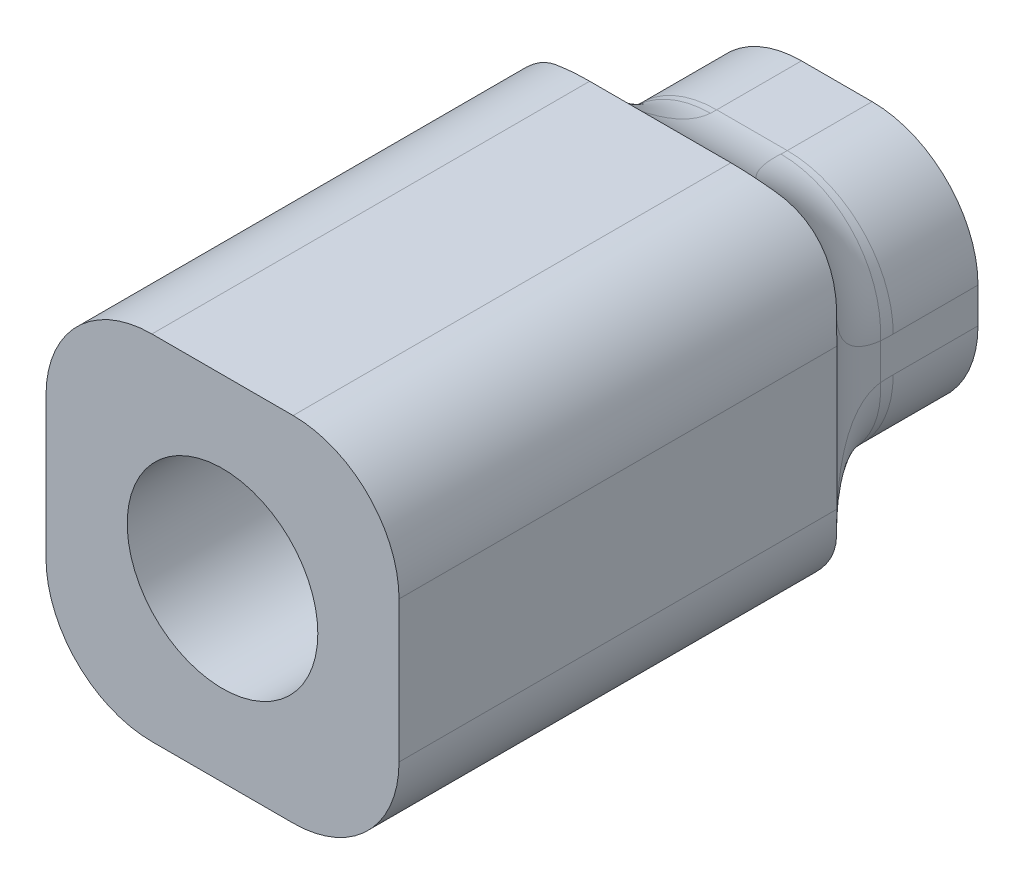
SolidWorks part; units mm, degrees
material "Custom Plastic"
ref_plane "X-Y Datum" through (0, 0, 0) normal (0, 0, 1) x (1, 0, 0)
ref_plane "X-Z Datum" through (0, 0, 0) normal (0, 1, 0) x (1, 0, 0)
ref_plane "Y-Z Datum" through (0, 0, 0) normal (1, 0, 0) x (0, 0, -1)
sketch "Sketch1" plane through (0, 0, 0) normal (0, 0, 1) x (1, 0, 0)
  line L1 (-4, 3.5) -> (4, 3.5)
  line L2 (-4, 3.5) -> (-4, -3.5)
  line L3 (-4, -3.5) -> (4, -3.5)
  line L4 (4, 3.5) -> (4, -3.5)
  line L5 (-4, 3.5) -> (4, -3.5) construction
  line L6 (-4, -3.5) -> (4, 3.5) construction
  circle A0 centre (0, 0) radius 2.7
  point P0 (0, 0)
  dimension "D3" = 5.4
  dimension "D1" = 8
  dimension "D2" = 7
extrude "Boss-Extrude1" add sketch "Sketch1" along normal blind 5
sketch "Sketch2" plane through (0, 0, 5) normal (0, 0, 1) x (1, 0, 0)
  line L1 (-5, 5) -> (5, 5)
  line L2 (-5, 5) -> (-5, -5)
  line L3 (-5, -5) -> (5, -5)
  line L4 (5, 5) -> (5, -5)
  line L5 (-5, 5) -> (5, -5) construction
  line L6 (-5, -5) -> (5, 5) construction
  circle A0 centre (0, 0) radius 2.7 construction
  circle A1 centre (0, 0) radius 2.7
  point P0 (0, 0)
  dimension "D1" = 10
  dimension "D2" = 10
extrude "Boss-Extrude2" add sketch "Sketch2" along normal blind 12.4
fillet "Fillet1" radius 3 4 edges at (4, 0, 5) (0, 3.5, 5) (-4, 0, 5) (0, -3.5, 5)
fillet "Fillet2" radius 3 16 edges at (-4, -3.5, 1.201) (-4, -3.5055, 2.5833) (-4, 3.5, 1.201) (-4, 3.5055, 2.5833) (4, 3.5, 1.201) (4, 3.5055, 2.5833) (4, -3.5, 1.201) (4, -3.5055, 2.5833) (5, -5, 11.2) (5, 5, 11.2) (-5, 5, 11.2) (-5, -5, 11.2) (-4.1075, -3.7325, 3.5598) (-4.4343, 4.1921, 4.3186) (4.1075, 3.7325, 3.5598) (4.1075, -3.7325, 3.5598)
